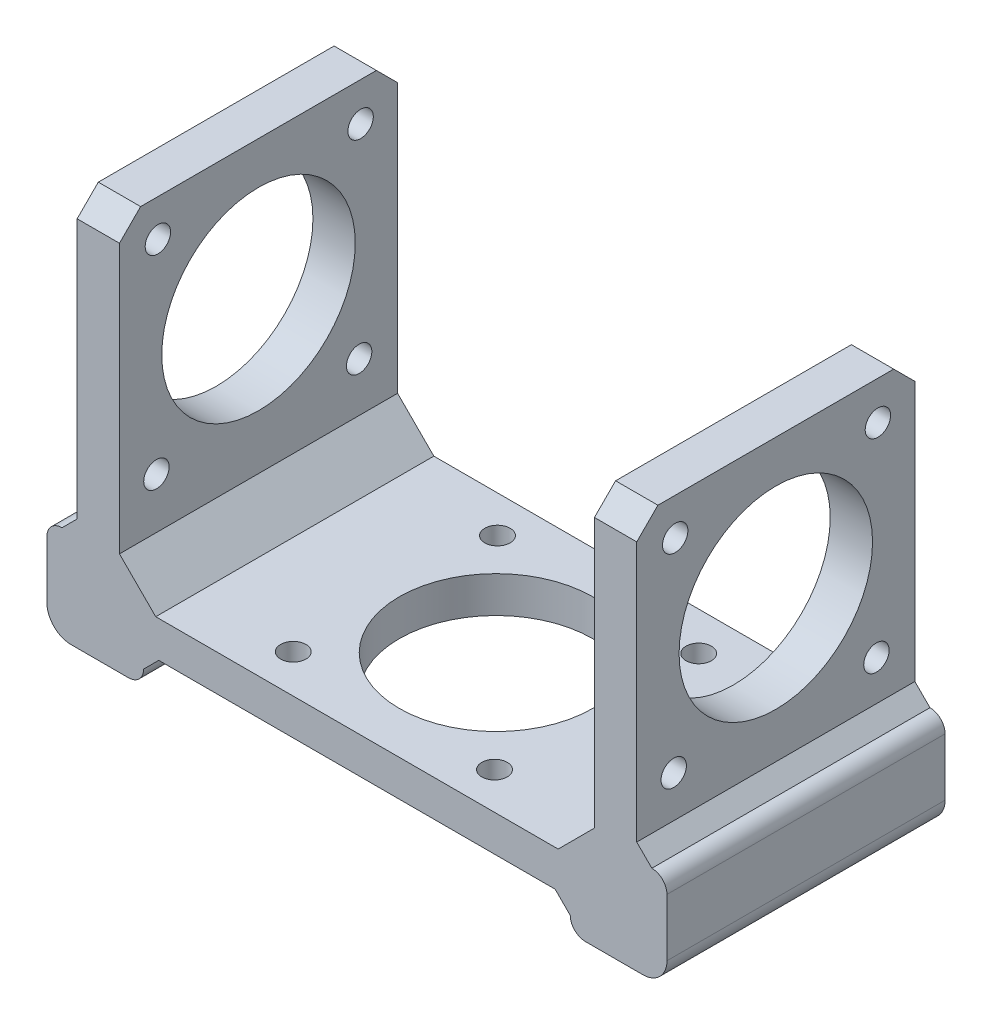
SolidWorks part; units mm, degrees
material "PA Type 6"
ref_plane "Płaszczyzna przednia" through (0, 0, 0) normal (0, 0, 1) x (1, 0, 0)
ref_plane "Płaszczyzna górna" through (0, 0, 0) normal (0, 1, 0) x (1, 0, 0)
ref_plane "Płaszczyzna prawa" through (0, 0, 0) normal (1, 0, 0) x (0, 0, -1)
sketch "Sketch1" plane through (0, 0, 0) normal (0, 1, 0) x (1, 0, 0)
  line L1 (0, 0) -> (92.56, 0)
  line L2 (0, 0) -> (0, 46)
  line L3 (0, 46) -> (92.56, 46)
  line L4 (92.56, 0) -> (92.56, 46)
  dimension "D1" = 92.56
  dimension "D2" = 46
extrude "Boss-Extrude1" add sketch "Sketch1" along normal blind 6
sketch "Sketch2" plane through (0, 6, 0) normal (0, 1, 0) x (1, 0, 0)
  line L0 (0, 0) -> (92.56, 0) construction
  line L1 (92.56, 46) -> (85.56, 46)
  line L2 (92.56, 46) -> (92.56, 0)
  line L3 (92.56, 0) -> (85.56, 0)
  line L4 (85.56, 46) -> (85.56, 0)
  line L6 (0, 46) -> (7, 46)
  line L7 (0, 46) -> (0, 0)
  line L8 (0, 0) -> (7, 0)
  line L9 (7, 46) -> (7, 0)
  dimension "D1" = 7
extrude "Boss-Extrude2" add sketch "Sketch2" along normal blind 54
sketch "Sketch3" plane through (92.56, 0, 0) normal (1, 0, 0) x (0, 0, -1)
  line L0 (0, 0) -> (46, 0) construction
  line L1 (23, 37) -> (23, 0) construction
  circle A0 centre (23, 37) radius 16
  dimension "D1" = 32
  dimension "D2" = 37
extrude "Cut-Extrude1" cut sketch "Sketch3" against normal through all
sketch "Sketch4" plane through (0, 6, 0) normal (0, 1, 0) x (1, 0, 0)
  line L0 (7, 46) -> (85.56, 0) construction
  line L1 (85.56, 0) -> (85.56, 46) construction
  line L2 (85.56, 46) -> (7, 0) construction
  circle A0 centre (46.28, 23) radius 16
  dimension "D1" = 32
extrude "Cut-Extrude2" cut sketch "Sketch4" against normal through all
sketch "Sketch5" plane through (0, 0, 0) normal (-1, 0, 0) x (0, 0, 1)
  line L0 (-46, 37) -> (-46, 60)
  line L1 (-46, 60) -> (0, 60)
  line L2 (0, 60) -> (0, 37)
  arc A0 (0, 37) -> (-46, 37) centre (-23, 37) ccw
extrude "Cut-Extrude3" [suppressed] cut sketch "Sketch5" against normal through all
hole_wizard "Ø4.2 (4.2) Diameter Hole1" positions "Sketch6" profile "Sketch7" hole size "Ø4.2" standard "DIN" end condition through all
sketch "Sketch6" plane through (0, 0, 0) normal (0, -1, 0) x (-1, 0, 0)
  point P0 (-63.1656, 39.6421)
  point P3 (-29.6379, 39.8856)
  point P6 (-29.3944, 6.3579)
  point P9 (-62.9221, 6.1144)
sketch "Sketch7" plane through (63.1656, 0, -39.6421) normal (1, 0, 0) x (0, 0, -1)
  line L0 (0, 0) -> (0, 60)
  line L1 (0, 60) -> (2.1, 60)
  line L2 (2.1, 60) -> (2.1, 0)
  line L5 (2.1, 0) -> (0, 0)
  line L11 (0, -6.35) -> (0, 107.95) construction
  dimension "Thru Hole Dia." = 4.2
  dimension "Thru Hole Depth" = 60
hole_wizard "Ø4.2 (4.2) Diameter Hole2" positions "Sketch8" profile "Sketch9" hole size "Ø4.2" standard "DIN" end condition through all
sketch "Sketch8" plane through (0, 0, 0) normal (-1, 0, 0) x (0, 0, 1)
  point P0 (-39.8856, 53.6421)
  point P3 (-6.3579, 53.8856)
  point P6 (-6.1144, 20.3579)
  point P9 (-39.6421, 20.1144)
sketch "Sketch9" plane through (0, 53.6421, -39.8856) normal (0, 1, 0) x (0, 0, 1)
  line L0 (0, 0) -> (0, 92.56)
  line L1 (0, 92.56) -> (2.1, 92.56)
  line L2 (2.1, 92.56) -> (2.1, 0)
  line L5 (2.1, 0) -> (0, 0)
  line L11 (0, -6.35) -> (0, 107.95) construction
  dimension "Thru Hole Dia." = 4.2
  dimension "Thru Hole Depth" = 92.56
chamfer "Chamfer1" distance 3.5 angle 45 4 edges at (3.5, 60, 0) (3.5, 60, -46) (89.06, 60, 0) (89.06, 60, -46)
chamfer "Chamfer2" distance 6 angle 45 2 edges at (7, 6, -23) (85.56, 6, -23)
sketch "Sketch10" plane through (0, 0, -46) normal (0, 0, -1) x (-1, 0, 0)
  line L0 (0, 11) -> (5, 11)
  line L1 (0, 56.5) -> (0, 0) construction
  line L2 (5, 11) -> (5, -5)
  line L3 (5, -5) -> (-11, -5)
  line L4 (-11, -5) -> (-11, 0)
  line L5 (-92.56, 0) -> (0, 0) construction
  line L6 (-11, 0) -> (0, 0)
  line L7 (0, 0) -> (0, 11)
  line L8 (-46.28, 6) -> (-46.28, 14.0709) construction
  line L9 (-79.56, 6) -> (-13, 6) construction
  line L10 (-81.56, 0) -> (-92.56, 0)
  line L11 (-81.56, -5) -> (-81.56, 0)
  line L12 (-97.56, -5) -> (-81.56, -5)
  line L13 (-97.56, 11) -> (-97.56, -5)
  line L14 (-92.56, 11) -> (-97.56, 11)
  line L15 (-92.56, 0) -> (-92.56, 11)
  dimension "D1" = 16
  dimension "D2" = 5
extrude "Boss-Extrude3" add sketch "Sketch10" against normal up to surface (46 mm away) up to face at (46.28, 26.2, 0)
fillet "Fillet1" radius 2.5 4 edges at (-5, 11, -23) (11, -5, -23) (97.56, 11, -23) (81.56, -5, -23)
chamfer "Chamfer3" distance 2.5 angle 45 4 edges at (92.56, 11, -23) (81.56, 0, -23) (11, 0, -23) (0, 11, -23)
fillet "Fillet2" radius 4 2 edges at (-5, -5, -23) (97.56, -5, -23)
